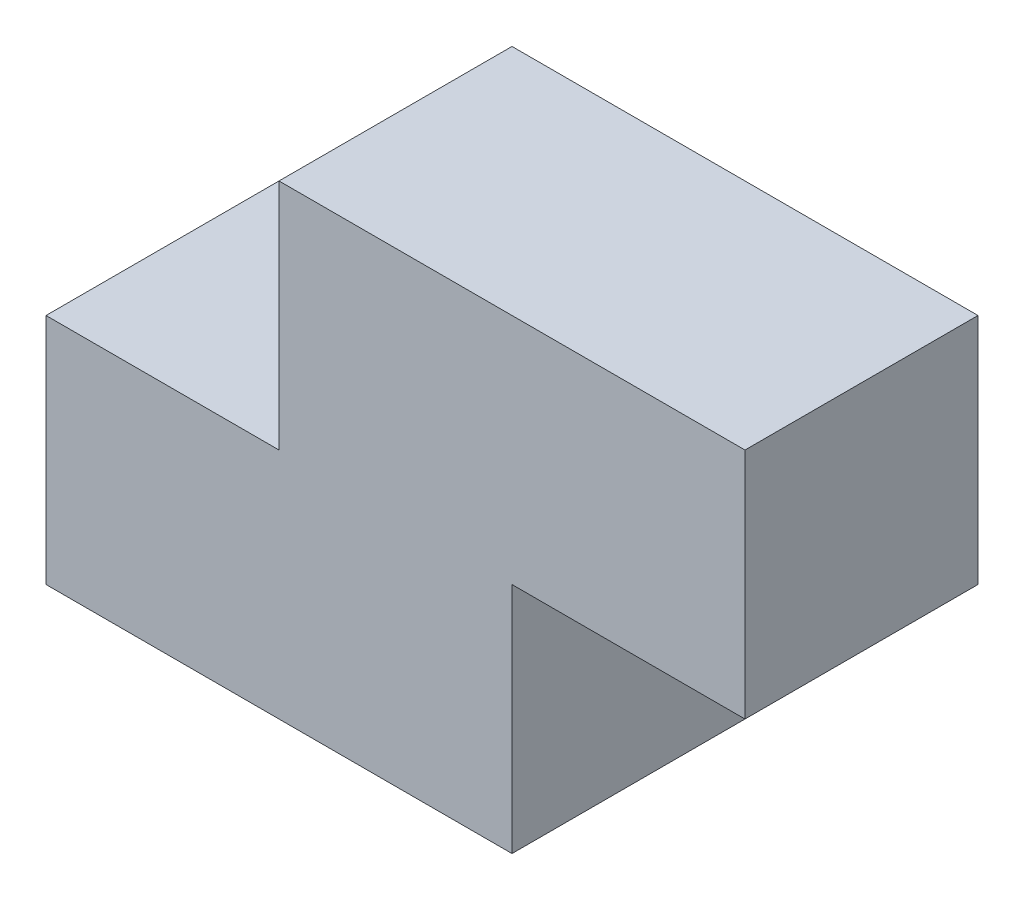
SolidWorks part; units mm, degrees
ref_plane "前基準面" through (0, 0, 0) normal (0, 0, 1) x (1, 0, 0)
ref_plane "上基準面" through (0, 0, 0) normal (0, 1, 0) x (1, 0, 0)
ref_plane "右基準面" through (0, 0, 0) normal (1, 0, 0) x (0, 0, -1)
ref_plane "平面1"
sketch "草圖1" plane through (0, 0, 0) normal (0, 0, 1) x (1, 0, 0)
  line L0 (0, 0) -> (60, 0)
  line L1 (60, 0) -> (60, 30)
  line L2 (60, 30) -> (90, 30)
  line L3 (90, 30) -> (90, 60)
  line L4 (90, 60) -> (30, 60)
  line L5 (30, 60) -> (30, 30)
  line L6 (30, 30) -> (0, 30)
  line L7 (0, 30) -> (0, 0)
  dimension "D1" = 60
  dimension "D2" = 30
  dimension "D3" = 30
  dimension "D4" = 30
  dimension "D5" = 60
  dimension "D6" = 30
  dimension "D7" = 30
extrude "擠出1" add sketch "草圖1" along normal blind 15 and the other way blind 15
